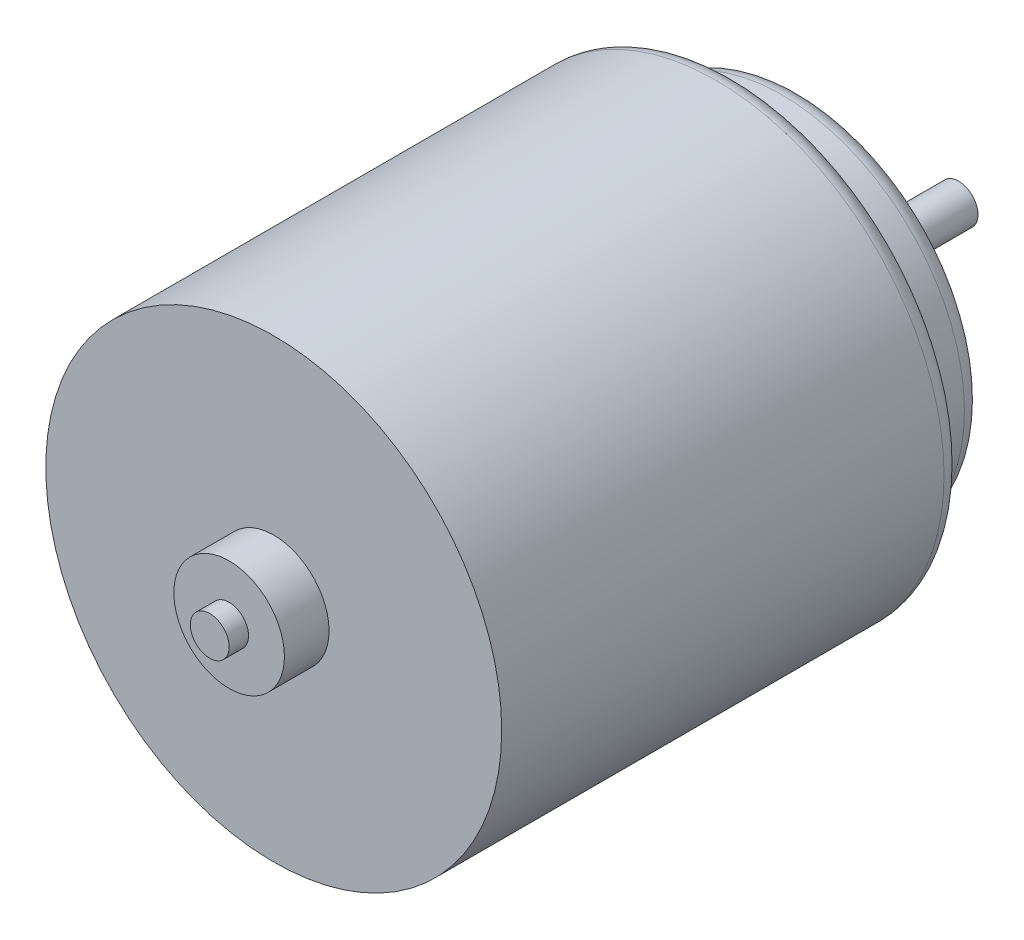
SolidWorks part; units mm, degrees
ref_plane "Front" through (0, 0, 0) normal (0, 0, 1) x (1, 0, 0)
ref_plane "Top" through (0, 0, 0) normal (0, 1, 0) x (1, 0, 0)
ref_plane "Right" through (0, 0, 0) normal (1, 0, 0) x (0, 0, -1)
sketch "Sketch1" plane through (0, 0, 0) normal (0, 0, 1) x (1, 0, 0)
  circle A0 centre (0, 0) radius 11.75
  circle A1 centre (0, 0) radius 9.4
  circle A2 centre (0, 0) radius 4.25
  circle A3 centre (0, 0) radius 1
  circle A4 centre (0, 0) radius 2.85
  dimension "D1" = 23.5
  dimension "D2" = 18.8
  dimension "D3" = 8.5
  dimension "D4" = 2
  dimension "D5" = 5.7
extrude "Boss-Extrude1" add sketch "Sketch1" against normal blind 23.8 contours A0 A1 region at (-11.4177, 0, 0)
extrude "Boss-Extrude2" add sketch "Sketch1<3>" against normal blind 27.2 contours A1 A2 region at (-9.1341, 0, 0)
sketch "Sketch1<3>" plane through (0, 0, 0) normal (0, 0, 1) x (1, 0, 0) same geometry as "Sketch1"
extrude "Boss-Extrude3" add sketch "Sketch1<4>" against normal blind 29.4 contours A2 A4 region at (-4.1298, 0, 0)
sketch "Sketch1<4>" plane through (0, 0, 0) normal (0, 0, 1) x (1, 0, 0) same geometry as "Sketch1"
extrude "Boss-Extrude4" add sketch "Sketch1<5>" along normal blind 2.3 and the other way blind 29.4 contours A4
sketch "Sketch1<5>" plane through (0, 0, 0) normal (0, 0, 1) x (1, 0, 0) same geometry as "Sketch1"
extrude "Boss-Extrude5" add sketch "Sketch1<6>" along normal blind 3.3 and the other way blind 35.3 contours A3
sketch "Sketch1<6>" plane through (0, 0, 0) normal (0, 0, 1) x (1, 0, 0) same geometry as "Sketch1"
fillet "Fillet1" radius 1 2 edges at (9.4, 0, -27.2) (11.75, 0, -23.8)
